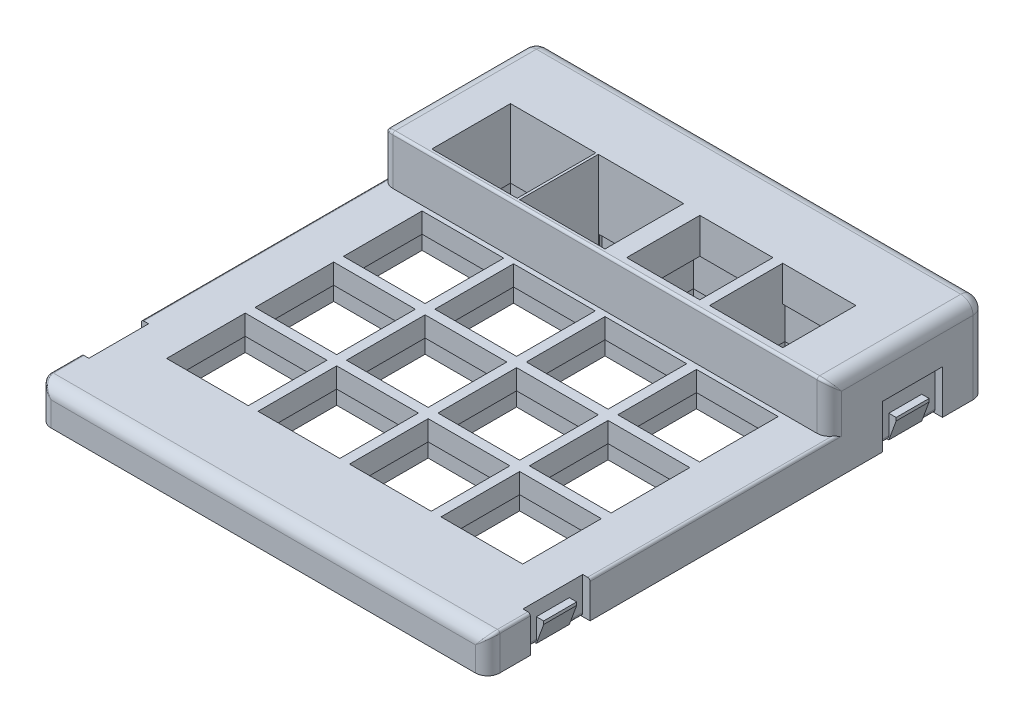
SolidWorks part; units mm, degrees
ref_plane "Ebene vorne" through (0, 0, 0) normal (0, 0, 1) x (1, 0, 0)
ref_plane "Ebene oben" through (0, 0, 0) normal (0, 1, 0) x (1, 0, 0)
ref_plane "Ebene rechts" through (0, 0, 0) normal (1, 0, 0) x (0, 0, -1)
ref_plane "Ebene1" through (0, 1.2, 0) normal (0, 1, 0) x (1, 0, 0)
sketch "Skizze2" plane through (0, 1.2, 0) normal (0, 1, 0) x (1, 0, 0)
  line L1 (-1.8, -1.8) -> (71.8, -1.8)
  line L2 (-1.8, -1.8) -> (-1.8, 79.8)
  line L3 (-1.8, 79.8) -> (71.8, 79.8)
  line L4 (71.8, -1.8) -> (71.8, 79.8)
  dimension "D1" = 79.8
  dimension "D2" = 1.8
  dimension "D3" = 71.8
  dimension "D4" = 1.8
extrude "Aufsatz-Linear austragen1" add sketch "Skizze2" along normal blind 6
surface "Oberfläche-Offset1" parameters "D1"=0
sketch "Skizze3" plane through (0, 1.2, 0) normal (0, 1, 0) x (1, 0, 0)
  line L1 (19.2, 11.55) -> (5.8, 11.55)
  line L2 (19.2, 11.55) -> (19.2, 24.45)
  line L3 (19.2, 24.45) -> (5.8, 24.45)
  line L4 (5.8, 11.55) -> (5.8, 24.45)
  line L6 (6.5, 24) -> (6.5, 12) construction
  line L7 (18.5, 12) -> (18.5, 24) construction
  line L8 (6.5, 12) -> (18.5, 12) construction
  line L10 (18.5, 24) -> (6.5, 24) construction
  dimension "D1" = 0.7
  dimension "D2" = 0.7
  dimension "D3" = 0.45
  dimension "D4" = 0.45
extrude "Schnitt-Linear austragen1" cut sketch "Skizze3" along normal through all
pattern_linear "Lineares Muster1" count 4 spacing 14.5 along (0, 0, -1) count 4 spacing 15 along (1, 0, 0) of "Schnitt-Linear austragen1"
sketch "Skizze4" plane through (0, 1.2, 0) normal (0, 1, 0) x (1, 0, 0)
  line L0 (19.2, 24.45) -> (5.8, 24.45) construction
  line L1 (19.6, 11.15) -> (5.4, 11.15)
  line L2 (19.6, 11.15) -> (19.6, 24.85)
  line L3 (19.6, 24.85) -> (5.4, 24.85)
  line L4 (5.4, 11.15) -> (5.4, 24.85)
  line L5 (19.2, 11.55) -> (19.2, 24.45) construction
  line L6 (5.8, 11.55) -> (19.2, 11.55) construction
  line L7 (5.8, 24.45) -> (5.8, 11.55) construction
  dimension "D1" = 0.4
  dimension "D2" = 0.4
  dimension "D3" = 0.4
  dimension "D4" = 0.4
extrude "Schnitt-Linear austragen2" cut sketch "Skizze4" along normal blind 2.7
pattern_linear "Lineares Muster2" count 4 spacing 14.5 along (0, 0, -1) count 4 spacing 15 along (1, 0, 0) of "Schnitt-Linear austragen2"
ref_plane "true_left" through (-1.8, 0, 0) normal (1, 0, 0) x (0, 0, -1)
ref_plane "Ebene4" through (0, 0, -39) normal (0, 0, 1) x (1, 0, 0)
sketch "Skizze6" plane through (-1.8, 0, 0) normal (1, 0, 0) x (0, 0, -1)
  line L0 (72.8, 7.2) -> (63, 7.2)
  line L1 (72.8, 1.2) -> (70.6, 1.2)
  line L4 (70.6, 1.2) -> (70.6, 5)
  line L7 (70.6, 5) -> (65.2, 5)
  line L10 (63, 7.2) -> (63, 1.2)
  line L11 (63, 1.2) -> (65.2, 1.2)
  line L12 (65.2, 5) -> (65.2, 1.2)
  line L13 (72.8, 7.2) -> (72.8, 1.2)
  line L14 (55, 1.2) -> (-55, 1.2) construction
  line L15 (39, 3.3) -> (39, -3.3) construction
  line L16 (5.2, 7.2) -> (15, 7.2)
  line L17 (15, 7.2) -> (15, 1.2)
  line L18 (15, 1.2) -> (12.8, 1.2)
  line L19 (12.8, 5) -> (12.8, 1.2)
  line L20 (7.4, 5) -> (12.8, 5)
  line L21 (7.4, 1.2) -> (7.4, 5)
  line L22 (5.2, 1.2) -> (7.4, 1.2)
  line L23 (5.2, 7.2) -> (5.2, 1.2)
  line L24 (0, 3.3) -> (0, -3.3) construction
  dimension "D1" = 2.2
  dimension "D2" = 2.2
  dimension "D3" = 6
  dimension "D4" = 63
  dimension "D5" = 5.4
extrude "Schnitt-Linear austragen6" cut sketch "Skizze6" along normal blind 1.2
ref_plane "Ebene5" through (35, 0, 0) normal (1, 0, 0) x (0, 0, -1)
mirror "Spiegeln1" about plane through (35, 0, 0) normal (1, 0, 0) of "Schnitt-Linear austragen6"
fillet "Verrundung1" radius 0.6 8 edges at (70.6, 1.2, -71.7) (70.6, 1.2, -64.1) (70.6, 1.2, -13.9) (70.6, 1.2, -6.3) (-0.6, 1.2, -13.9) (-0.6, 1.2, -6.3) (-0.6, 1.2, -71.7) (-0.6, 1.2, -64.1)
chamfer "Fase1" distance 1.2 angle 70 4 edges at (71.8, 1.2, -67.9) (71.8, 1.2, -10.1) (-1.8, 1.2, -10.1) (-1.8, 1.2, -67.9) first distance on face at (35, 1.2, -39)
ref_plane "Ebene6" through (0, 7.2, 0) normal (0, 1, 0) x (1, 0, 0)
sketch "Skizze7" plane through (0, 7.2, 0) normal (0, 1, 0) x (1, 0, 0)
  line L1 (-1.8, 54.25) -> (71.8, 54.25)
  line L2 (-1.8, 54.25) -> (-1.8, 79.8)
  line L3 (-1.8, 79.8) -> (71.8, 79.8)
  line L4 (71.8, 54.25) -> (71.8, 79.8)
  line L5 (0, -3.3) -> (0, 3.3) construction
  line L6 (-3.3, 0) -> (3.3, 0) construction
  line L7 (34.2, 55.05) -> (20.2, 55.05)
  line L8 (5.8, 55.05) -> (19.8, 55.05)
  line L9 (5.8, 55.05) -> (5.8, 67.95)
  line L10 (5.8, 67.95) -> (19.8, 67.95)
  line L11 (19.8, 55.05) -> (19.8, 67.95)
  line L12 (34.2, 55.05) -> (34.2, 67.95)
  line L13 (34.2, 67.95) -> (20.2, 67.95)
  line L14 (20.2, 55.05) -> (20.2, 67.95)
  line L15 (37.2, 55.6) -> (49.2, 55.6)
  line L16 (37.2, 55.6) -> (37.2, 67.6)
  line L17 (37.2, 67.6) -> (49.2, 67.6)
  line L18 (49.2, 55.6) -> (49.2, 67.6)
  line L19 (50.8, 55.6) -> (62.8, 55.6)
  line L20 (50.8, 55.6) -> (50.8, 67.6)
  line L21 (50.8, 67.6) -> (62.8, 67.6)
  line L22 (62.8, 55.6) -> (62.8, 67.6)
  dimension "D1" = 1.8
  dimension "D2" = 73.6
  dimension "D3" = 79.8
  dimension "D4" = 54.25
  dimension "D5" = 67.95
  dimension "D6" = 5.8
  dimension "D7" = 55.05
  dimension "D8" = 14
  dimension "D9" = 0.4
  dimension "D10" = 14
  dimension "D11" = 12
  dimension "D12" = 12
  dimension "D13" = 1.6
  dimension "D14" = 55.6
  dimension "D15" = 49.2
extrude "Aufsatz-Linear austragen2" add sketch "Skizze7" along normal blind 8
sketch "Skizze8" plane through (0, 7.2, 0) normal (0, 1, 0) x (1, 0, 0)
  line L1 (5.8, 55.05) -> (19.8, 55.05)
  line L2 (5.8, 55.05) -> (5.8, 67.95)
  line L3 (5.8, 67.95) -> (19.8, 67.95)
  line L4 (19.8, 55.05) -> (19.8, 67.95)
  line L5 (20.2, 67.95) -> (34.2, 67.95)
  line L6 (20.2, 67.95) -> (20.2, 55.05)
  line L7 (20.2, 55.05) -> (34.2, 55.05)
  line L8 (34.2, 67.95) -> (34.2, 55.05)
  dimension "D1" = 14
  dimension "D3" = 55.05
  dimension "D4" = 0.4
  dimension "D5" = 5.8
  dimension "D6" = 67.95
extrude "Schnitt-Linear austragen8" cut sketch "Skizze8" against normal blind 8
chamfer "Fase2" distance 1.2 angle 45 2 edges at (-1.8, 7.2, -67.9) (71.8, 7.2, -67.9)
sketch "Skizze9" plane through (0, 7.2, 0) normal (0, 1, 0) x (1, 0, 0)
  line L0 (64.2, 67.95) -> (50.8, 67.95) construction
  line L1 (64.2, 55.05) -> (50.8, 55.05)
  line L2 (64.2, 55.05) -> (64.2, 67.95)
  line L3 (64.2, 67.95) -> (50.8, 67.95)
  line L4 (50.8, 55.05) -> (50.8, 67.95)
  line L5 (49.2, 55.05) -> (35.8, 55.05)
  line L6 (49.2, 55.05) -> (49.2, 67.95)
  line L7 (49.2, 67.95) -> (35.8, 67.95)
  line L8 (35.8, 55.05) -> (35.8, 67.95)
  line L9 (64.2, 55.05) -> (64.2, 67.95) construction
  line L10 (50.8, 55.05) -> (64.2, 55.05) construction
  line L11 (20.4, 55.05) -> (34.2, 55.05) construction
  line L12 (35.8, 55.05) -> (49.2, 55.05) construction
  line L13 (35.8, 55.05) -> (49.2, 55.05) construction
  line L14 (35.8, 67.95) -> (35.8, 55.05) construction
  dimension "D1" = 1.6
extrude "Schnitt-Linear austragen9" cut sketch "Skizze9" along normal blind 2.2
fillet "Verrundung2" radius 2 10 edges at (-1.8, 11.2, -54.25) (-1.8, 15.2, -67.025) (71.8, 15.2, -67.025) (71.8, 11.2, -54.25) (71.8, 4.2, 1.8) (35, 7.2, 1.8) (-1.8, 4.2, 1.8) (35, 15.2, -79.8) (71.8, 8.2, -79.8) (-1.8, 8.2, -79.8)
fillet "Verrundung3" radius 0.4 9 edges at (-1.2142, 14.6142, -54.8358) (71.2142, 14.6142, -54.8358) (35, 15.2, -54.25) (-1.2142, 6.6142, 1.2142) (71.2142, 6.6142, 1.2142) (-1.8, 7.2, -2.7) (-1.8, 7.2, -35.625) (71.8, 7.2, -2.7) (71.8, 7.2, -35.625)
